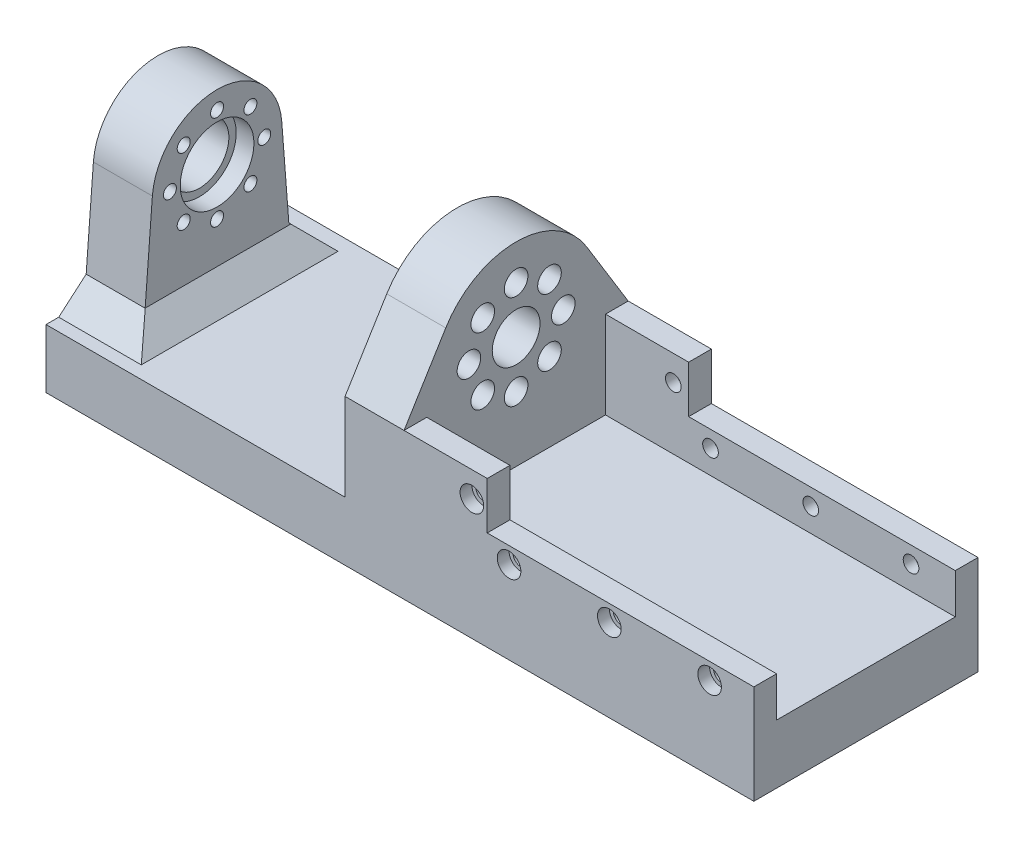
SolidWorks part; units mm, degrees
ref_plane "Front Plane" through (0, 0, 0) normal (0, 0, 1) x (1, 0, 0)
ref_plane "Top Plane" through (0, 0, 0) normal (0, 1, 0) x (1, 0, 0)
ref_plane "Right Plane" through (0, 0, 0) normal (1, 0, 0) x (0, 0, -1)
sketch "Sketch1" plane through (0, 0, 0) normal (0, 1, 0) x (1, 0, 0)
  line L1 (0, 0) -> (120, 0)
  line L2 (0, 0) -> (0, 38)
  line L3 (0, 38) -> (120, 38)
  line L4 (120, 0) -> (120, 38)
  dimension "D1" = 38
  dimension "D2" = 120
extrude "Boss-Extrude1" add sketch "Sketch1" along normal blind 10
sketch "Sketch3" plane through (0, 0, 0) normal (-1, 0, 0) x (0, 0, 1)
  line L0 (-29.9673, 29.8469) -> (-31.5, 10)
  line L1 (-38, 10) -> (0, 10) construction
  line L2 (-8.0327, 29.8469) -> (-6.5, 10)
  line L3 (-31.5, 10) -> (-6.5, 10)
  line L4 (-38, 0) -> (0, 0) construction
  circle A0 centre (-19, 29) radius 4.05
  arc A1 (-8.0327, 29.8469) -> (-29.9673, 29.8469) centre (-19, 29) ccw
  point P11 (-19, 0)
  point P12 (-19, 10)
  dimension "D2" = 8.1
  dimension "D3" = 22
  dimension "D1" = 19
  dimension "D4" = 25
extrude "Boss-Extrude2" add sketch "Sketch3" against normal blind 10
sketch "Sketch4" plane through (0, 0, 0) normal (-1, 0, 0) x (0, 0, 1)
  line L0 (-19, 37) -> (-19, 29) construction
  circle A0 centre (-19, 37) radius 1.1
  dimension "D1" = 2.2
  dimension "D2" = 8
extrude "Cut-Extrude1" cut sketch "Sketch4" against normal through all
sketch "Sketch5" plane through (0, 0, 0) normal (-1, 0, 0) x (0, 0, 1)
  circle A0 centre (-19, 37) radius 2
  dimension "D1" = 4
extrude "Cut-Extrude2" cut sketch "Sketch5" against normal blind 5.6
pattern_circular "CirPattern2" count 8 over 360 about axis through (0, 29, -19) along (1, 0, 0) of "Cut-Extrude1", "Cut-Extrude2"
ref_plane "Plane1" through (30.35, 0, 0) normal (1, 0, 0) x (0, 0, -1)
mirror "Mirror1" about plane through (30.35, 0, 0) normal (1, 0, 0) of "CirPattern2", "Boss-Extrude2", "Cut-Extrude1", "Cut-Extrude2"
sketch "Sketch6" plane through (120, 0, 0) normal (1, 0, 0) x (0, 0, -1)
  line L1 (0, 10) -> (3.85, 10)
  line L2 (0, 10) -> (0, 16.8)
  line L3 (0, 16.8) -> (3.85, 16.8)
  line L4 (3.85, 10) -> (3.85, 16.8)
  line L5 (38, 10) -> (34.15, 10)
  line L6 (38, 10) -> (38, 16.8)
  line L7 (38, 16.8) -> (34.15, 16.8)
  line L8 (34.15, 10) -> (34.15, 16.8)
  dimension "D1" = 30.3
  dimension "D2" = 6.8
extrude "Boss-Extrude3" add sketch "Sketch6" against normal blind 69.3
sketch "Sketch7" plane through (0, 0, 0) normal (0, 0, 1) x (1, 0, 0)
  line L0 (120, 16.8) -> (120, 0) construction
  line L1 (50.7, 16.8) -> (120, 16.8) construction
  circle A0 centre (112.5, 14) radius 1.325
  circle A1 centre (95.5, 14) radius 1.325
  circle A2 centre (78.5, 14) radius 1.325
  dimension "D1" = 7.5
  dimension "D2" = 2.65
  dimension "D5" = 2.8
  dimension "D3" = 17
  dimension "D4" = 34
extrude "Cut-Extrude3" cut sketch "Sketch7" against normal through all
ref_plane "Plane2" through (0, 0, -19) normal (0, 0, 1) x (1, 0, 0)
chamfer "Chamfer2" distance 4 angle 45 2 edges at (5, 10, -31.5) (5, 10, -6.5)
chamfer "Chamfer3" distance 4 angle 45 2 edges at (10, 10, -18.8262) (50.7, 10, -19)
sketch "Sketch10" plane through (0, 0, 0) normal (0, 0, 1) x (1, 0, 0)
  line L0 (120, 16.8) -> (120, 0) construction
  line L1 (50.7, 16.8) -> (74.8, 16.8)
  line L2 (50.7, 16.8) -> (50.7, 24.8)
  line L3 (50.7, 24.8) -> (74.8, 24.8)
  line L4 (74.8, 16.8) -> (74.8, 24.8)
  dimension "D1" = 45.2
  dimension "D2" = 8
extrude "Boss-Extrude5" add sketch "Sketch10" against normal up to surface (3.85 mm away) up to face at (112.5, 15.325, -3.85)
sketch "Sketch12" plane through (0, 0, 0) normal (0, 0, 1) x (1, 0, 0)
  circle A0 centre (72.2, 20.5) radius 1.325
  circle A2 centre (78.5, 14) radius 1.325 construction
  dimension "D1" = 6.5
  dimension "D2" = 6.3
extrude "Cut-Extrude5" cut sketch "Sketch12" against normal through all
sketch "Sketch13" plane through (0, 0, 0) normal (0, 0, 1) x (1, 0, 0)
  circle A0 centre (112.5, 14) radius 2
  circle A1 centre (95.5, 14) radius 2
  circle A2 centre (78.5, 14) radius 2
  circle A3 centre (72.2, 20.5) radius 2
  dimension "D1" = 4
extrude "Cut-Extrude6" cut sketch "Sketch13" against normal blind 2
sketch "Sketch14" plane through (0, 0, -38) normal (0, 0, -1) x (-1, 0, 0)
  line L1 (-50.7, 16.8) -> (-74.8, 16.8)
  line L2 (-50.7, 16.8) -> (-50.7, 24.8)
  line L3 (-50.7, 24.8) -> (-74.8, 24.8)
  line L4 (-74.8, 16.8) -> (-74.8, 24.8)
extrude "Boss-Extrude6" add sketch "Sketch14" against normal up to surface (3.85 mm away) up to face at (113.825, 14, -34.15)
sketch "Sketch15" plane through (60.7, 0, 0) normal (1, 0, 0) x (0, 0, -1)
  line L0 (0, 24.8) -> (3.85, 24.8)
  line L1 (3.85, 24.8) -> (3.85, 10)
  line L2 (3.85, 10) -> (6.5, 10)
  line L3 (6.5, 10) -> (8.0327, 29.8469)
  line L5 (19, 40) -> (19, 43)
  line L6 (7.0661, 36.32) -> (0, 24.8)
  arc A2 (29.9673, 29.8469) -> (8.0327, 29.8469) centre (19, 29) ccw construction
  arc A3 (19, 40) -> (8.0327, 29.8469) centre (19, 29) ccw
  arc A4 (19, 43) -> (7.0661, 36.32) centre (19, 29) ccw
  dimension "D1" = 14
extrude "Boss-Extrude7" add sketch "Sketch15" against normal up to surface (10 mm away) up to face at (50.7, 37, -20.1)
mirror "Mirror7" about plane through (0, 0, -19) normal (0, 0, 1) of "Boss-Extrude7", "Cut-Extrude6", "Cut-Extrude5"
sketch "Sketch17" plane through (10, 0, 0) normal (1, 0, 0) x (0, 0, -1)
  circle A0 centre (19, 29) radius 6.25
  dimension "D1" = 12.5
extrude "Cut-Extrude8" cut sketch "Sketch17" against normal blind 3
sketch "Sketch18" plane through (0, 0, 0) normal (-1, 0, 0) x (0, 0, 1)
  circle A0 centre (-19, 29) radius 5
  dimension "D1" = 10
extrude "Cut-Extrude9" cut sketch "Sketch18" against normal up to surface (10 mm away) up to face at (10, 29, -25.25)
